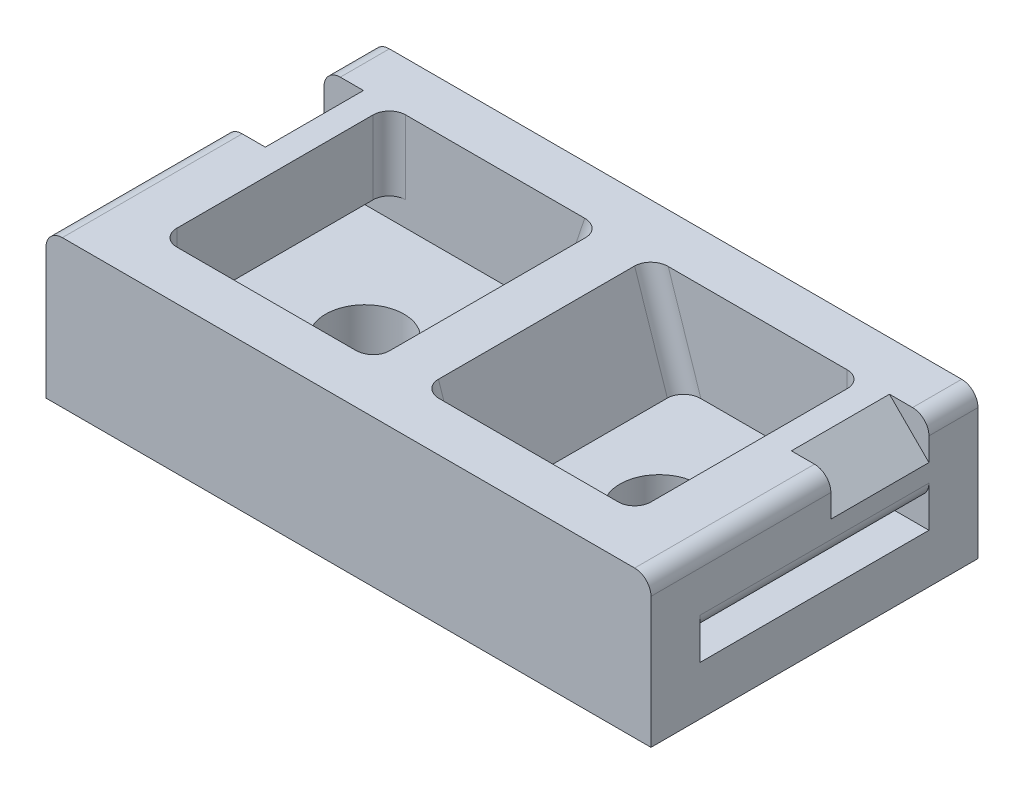
SolidWorks part; units mm, degrees
material "Windform LX 3.0"
ref_plane "Front Plane" through (0, 0, 0) normal (0, 0, 1) x (1, 0, 0)
ref_plane "Top Plane" through (0, 0, 0) normal (0, 1, 0) x (1, 0, 0)
ref_plane "Right Plane" through (0, 0, 0) normal (1, 0, 0) x (0, 0, -1)
sketch "Sketch1" plane through (0, 0, 0) normal (0, 1, 0) x (1, 0, 0)
  line L0 (-9.25, 0) -> (9.25, 0) construction
  line L1 (-9.25, 5) -> (9.25, 5)
  line L2 (-9.25, 5) -> (-9.25, -5)
  line L3 (-9.25, -5) -> (9.25, -5)
  line L4 (9.25, 5) -> (9.25, -5)
  line L5 (0, 5) -> (0, -5) construction
  line L6 (-7.25, 3.5) -> (-1.75, 3.5)
  line L7 (-7, 3.25) -> (-2, 3.25) construction
  line L8 (-7, 3.25) -> (-7, -3.25) construction
  line L9 (-7, -3.25) -> (-2, -3.25) construction
  line L10 (-2, 3.25) -> (-2, -3.25) construction
  line L11 (-1.75, 3.5) -> (-1.75, -3.5)
  line L12 (-7.25, -3.5) -> (-1.75, -3.5)
  line L13 (-7.25, 3.5) -> (-7.25, -3.5)
  line L14 (7.25, 3.5) -> (7.25, -3.5)
  line L15 (7.25, -3.5) -> (1.75, -3.5)
  line L16 (1.75, 3.5) -> (1.75, -3.5)
  line L17 (7.25, 3.5) -> (1.75, 3.5)
  point P9 (-7, 0)
  dimension "D1" = 5
  dimension "D2" = 6.5
  dimension "D3" = 2
  dimension "D4" = 0.25
  dimension "D5" = 2
  dimension "D6" = 1.5
extrude "Boss-Extrude1" add sketch "Sketch1" along normal blind 1.5 contours L6 L13 L12 L11 | L14 L17 L16 L15 | L4 L1 L2 L3 L17 L14 L15 L16 L13 L6 L11 L12 region at (0, 0, 0) region at (-4.5, 0, 0) region at (4.5, 0, 0)
extrude "Boss-Extrude2" add sketch "Sketch1<3>" along normal blind 4.5
sketch "Sketch1<3>" plane through (0, 0, 0) normal (0, 1, 0) x (1, 0, 0) same geometry as "Sketch1"
sketch "Sketch2" plane through (-9.25, 0, 0) normal (-1, 0, 0) x (0, 0, 1)
  line L0 (5, 4.5) -> (5, 0) construction
  line L1 (-3.5, 2.25) -> (3.5, 2.25)
  line L2 (-3.5, 2.25) -> (-3.5, 1.5)
  line L3 (-3.5, 1.5) -> (3.5, 1.5)
  line L4 (3.5, 2.25) -> (3.5, 1.5)
  line L5 (-5, 4.5) -> (-5, 0) construction
  line L6 (-5, 0) -> (5, 0) construction
  dimension "D1" = 1.5
  dimension "D2" = 1.5
  dimension "D3" = 1.5
  dimension "D4" = 0.75
extrude "Cut-Extrude1" cut sketch "Sketch2" against normal up to surface (2 mm away) up to face at (-7.25, 3, 0)
extrude "Cut-Extrude5" cut sketch "Sketch2<2>" against normal up to surface (18.5 mm away) from surface up to face at (9.25, 2.25, 0) starting at face at (7.25, 3, 0)
sketch "Sketch2<2>" plane through (-9.25, 0, 0) normal (-1, 0, 0) x (0, 0, 1) same geometry as "Sketch2"
ref_plane "Plane1" through (0, 0, 0) normal (0.7071, 0.7071, 0) x (0, 0, 1)
sketch "Sketch4" plane through (0, 0, 0) normal (0.7071, 0.7071, 0) x (0, 0, 1)
  line L0 (5, -9.7227) -> (5, 3.3588) construction
  line L1 (-0.5, -11.5593) -> (-3.5, -11.5593)
  line L2 (-0.5, -11.5593) -> (-0.5, -8.8692)
  line L3 (-0.5, -8.8692) -> (-3.5, -8.8692)
  line L4 (-3.5, -11.5593) -> (-3.5, -8.8692)
  line L5 (-5, 3.3588) -> (-5, -9.7227) construction
  line L8 (-5, -9.7227) -> (5, -9.7227) construction
  dimension "D1" = 5.5
  dimension "D2" = 1.5
  dimension "D3" = 0.8536
extrude "Cut-Extrude3" cut sketch "Sketch4" against normal through all and the other way through all
hole_wizard "M2 Clearance Hole1" positions "3DSketch1" profile "Sketch5" hole size "M2" standard "ISO"
sketch3d "3DSketch1"
  line L0 (-9.25, 1.5, -3.5) -> (-1.75, 1.5, -3.5) construction
  line L2 (-1.75, 1.5, -3.5) -> (-1.75, 1.5, 3.5) construction
  point P0 (-4.5, 1.5, 0)
  dimension "D1" = 3.5
  dimension "D2" = 2.75
sketch "Sketch5" plane through (-4.5, 1.5, 0) normal (1, 0, 0) x (0, 0, 1)
  line L0 (0, 0) -> (0, 2.321)
  line L1 (0, 2.321) -> (1.2, 1.6)
  line L2 (1.2, 1.6) -> (1.2, 0)
  line L5 (1.2, 0) -> (0, 0)
  line L10 (0, 2.321) -> (-1.2, 1.6) construction
  line L11 (0, -6.35) -> (0, 107.95) construction
  dimension "Hole Dia." = 2.4
  dimension "Hole Depth" = 1.6
  dimension "Drill Angle" = 118
mirror "Mirror4" about plane through (0, 0, 0) normal (1, 0, 0) of "Cut-Extrude3", "M2 Clearance Hole1"
chamfer "Chamfer1" distance 1 distance2 3 2 edges at (-1.75, 4.5, 0) (1.75, 4.5, 0) first distance on face at (-4.5, 4.5, 0)
fillet "Fillet2" radius 0.5 14 edges at (9.25, 2.25, 0) (-9.25, 2.25, 0) (-9.25, 4.5, 2.25) (-9.25, 4.5, -4.25) (7.25, 3.375, 3.5) (7.25, 3.375, -3.5) (9.25, 4.5, 2.25) (9.25, 4.5, -4.25) (1.25, 3, -3.5) (1.25, 3, 3.5) (-7.25, 3.375, 3.5) (-1.25, 3, 3.5) (-1.25, 3, -3.5) (-7.25, 3.375, -3.5)
